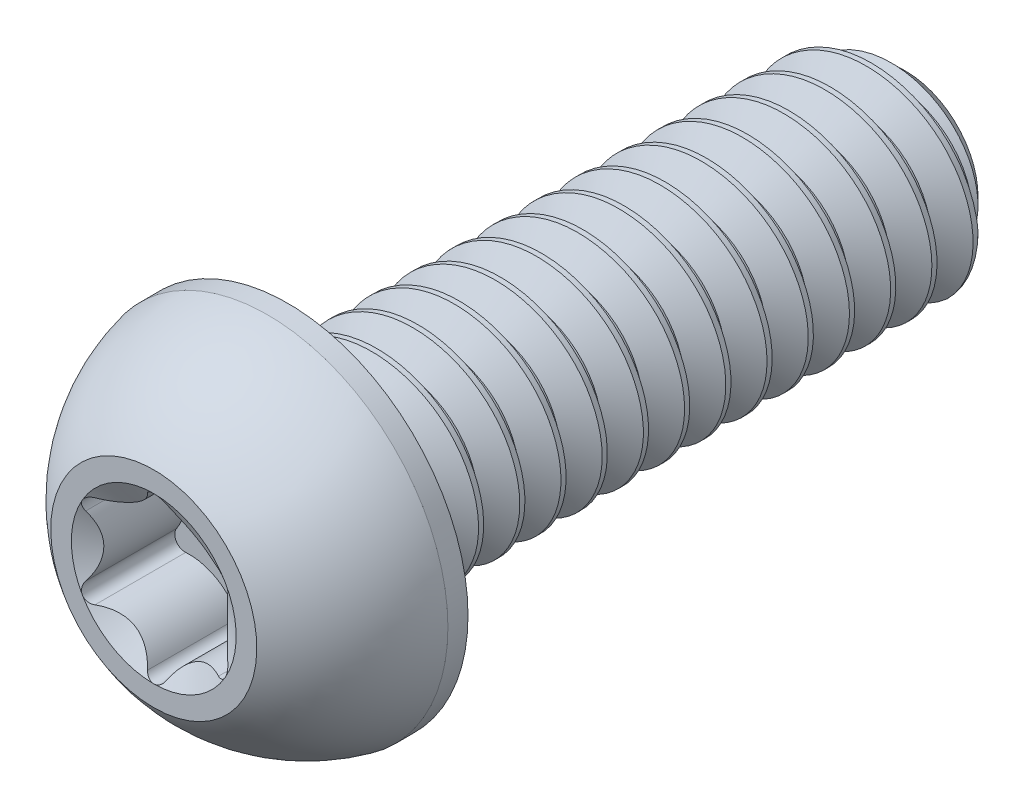
SolidWorks part; units mm, degrees
material "Alloy Steel"
ref_plane "Front" through (0, 0, 0) normal (0, 0, 1) x (1, 0, 0)
ref_plane "Top" through (0, 0, 0) normal (0, 1, 0) x (1, 0, 0)
ref_plane "Right" through (0, 0, 0) normal (1, 0, 0) x (0, 0, -1)
sketch "Sketch1" plane through (0, 0, 0) normal (1, 0, 0) x (0, 0, -1)
  line L2 (1.3, 1) -> (7.3, 1)
  line L3 (7.3, 1) -> (7.3, 0)
  line L4 (7.3, 0) -> (1.3, 0)
  line L6 (1.105, 1.75) -> (1.3, 1.75) construction
  line L7 (7.3, 1) -> (7.3, -1) construction
  line L8 (0, 0) -> (1.3, 0) construction
  line L9 (1.3, 1.75) -> (1.3, -1.75) construction
  line L11 (1.3, 1) -> (1.3, 0)
  line L14 (0, 0) -> (0, 1) construction
  arc A3 (0, 1) -> (1.105, 1.75) centre (1.4858, 0) cw construction
  dimension "D1" = 0.195
revolve "Revolve1" add sketch "Sketch1" angle 360 mid plane about L4
sketch "Sketch3" plane through (0, 0, -7.3) normal (0, 0, -1) x (-1, 0, 0)
  circle A0 centre (0, 0) radius 1
curve "Helix/Spiral1" pitch 0.4 height 6.4 radius 1 centre (0, 0, -7.3) axis (0, 0, 1) start towards (0, 1, 0)
sketch "Sketch2" plane through (0, 0, 0) normal (1, 0, 0) x (0, 0, -1)
  line L0 (7.3, 1) -> (7.65, 1)
  line L1 (7.65, 1) -> (7.5, 0.7402)
  line L2 (7.5, 0.7402) -> (7.45, 0.7402)
  line L3 (7.45, 0.7402) -> (7.3, 1)
  line L4 (7.375, 0.8701) -> (7.575, 0.8701) construction
  dimension "D1" = 60
  dimension "D2" = 0.05
  dimension "D3" = 0.2
chamfer "Chamfer1" distance 0.3 angle 45 1 edges at (0, 1, -7.3)
sweep "Cut-Sweep1" cut profiles "Sketch2" path "Helix/Spiral1" align with end faces yes
sketch "Sketch7" plane through (0, 0, 0) normal (1, 0, 0) x (0, 0, -1)
  line L0 (0, 0) -> (0, 1) construction
  line L6 (1.105, 1.75) -> (1.3, 1.75) construction
  line L8 (0, 0) -> (1.3, 0) construction
  line L11 (1.3, 1.75) -> (1.3, -1.75) construction
  line L12 (1.105, 1.75) -> (1.3, 1.75)
  line L13 (0, 0) -> (1.3, 0)
  line L15 (1.3, 1.75) -> (1.3, 0)
  line L16 (0, 1) -> (0, 0)
  arc A2 (1.105, 1.75) -> (0, 1) centre (1.4858, 0) ccw construction
  arc A3 (1.105, 1.75) -> (0, 1) centre (1.4858, 0) ccw
revolve "Revolve2" add sketch "Sketch7" angle 360 mid plane about L13
sketch "Sketch11" plane through (0, 0, 0) normal (0, 0, 1) x (1, 0, 0)
  line L0 (0, 0) -> (-0.6928, 0.4)
  line L1 (0, 0) -> (-0.6928, -0.4)
  line L2 (0, 0.8) -> (0, 0.7) construction
  line L3 (0, 0.7) -> (0, 0.6) construction
  line L4 (1.925, 0) -> (-1.925, 0) construction
  circle A0 centre (0, 0) radius 0.6 construction
  circle A1 centre (0, 0) radius 0.7 construction
  circle A2 centre (0, 0) radius 0.8 construction
  arc A3 (-0.6894, 0.2944) -> (-0.6894, -0.2944) centre (-1.1298, 0) cw
  arc A4 (-0.6894, 0.2944) -> (-0.6928, 0.4) centre (-0.6062, 0.35) cw
  arc A5 (-0.6894, -0.2944) -> (-0.6928, -0.4) centre (-0.6062, -0.35) ccw
  dimension "D1" = 1.2
  dimension "D2" = 1.6
  dimension "D3" = 30
extrude "Cut-Extrude4" cut sketch "Sketch11" against normal blind 0.91
pattern_circular "CirPattern1" count 6 over 360 of "Cut-Extrude4"
sketch "Sketch6" plane through (0, 0, 0) normal (0, 0, 1) x (1, 0, 0)
  circle A0 centre (0, 0) radius 0.8 construction
  circle A1 centre (0, 0) radius 0.8
extrude "Cut-Extrude3" cut sketch "Sketch6" against normal blind 0.91 draft 60
sketch "Sketch9" [suppressed] plane through (0, 0, -5.5) normal (0, 0, 1) x (1, 0, 0)
  circle A2 centre (0, 0) radius 5
extrude "Boss-Extrude2" [suppressed] add sketch "Sketch9" against normal offset from surface (13 mm away) 32 up to face at (0, 0.7, -7.3)
sketch "Sketch10" plane through (0, 0, 0) normal (1, 0, 0) x (0, 0, -1)
  line L0 (7.3, 1) -> (7.3, -1) construction
  point P0 (6.7, -1)
  dimension "D1" = 0.6
equation "\"D3@Helix/Spiral1\" = \"Lg@Sketch1\" + \"D4@Helix/Spiral1\""
equation "\"D2@Sketch2\" = \"D4@Helix/Spiral1\" * .125"
equation "\"D3@Sketch2\" = \"D4@Helix/Spiral1\" * .5"
equation "\"D1@Chamfer1\" = \"D4@Helix/Spiral1\" * .75"
equation "\"D1@Sketch1\" = \"Head Ht@Sketch1\" * .15"
equation "\"D1@Sketch10\" = \"D4@Helix/Spiral1\" * 1.5"
equation "\"D2@Sketch11\" = \"Dia@Sketch1\" * .8"
equation "\"D1@Sketch11\" = \"D2@Sketch11\" * .75"
equation "\"D1@Cut-Extrude4\" = \"Head Ht@Sketch1\" * .7"
equation "\"D1@Cut-Extrude3\" = \"D1@Cut-Extrude4\""
